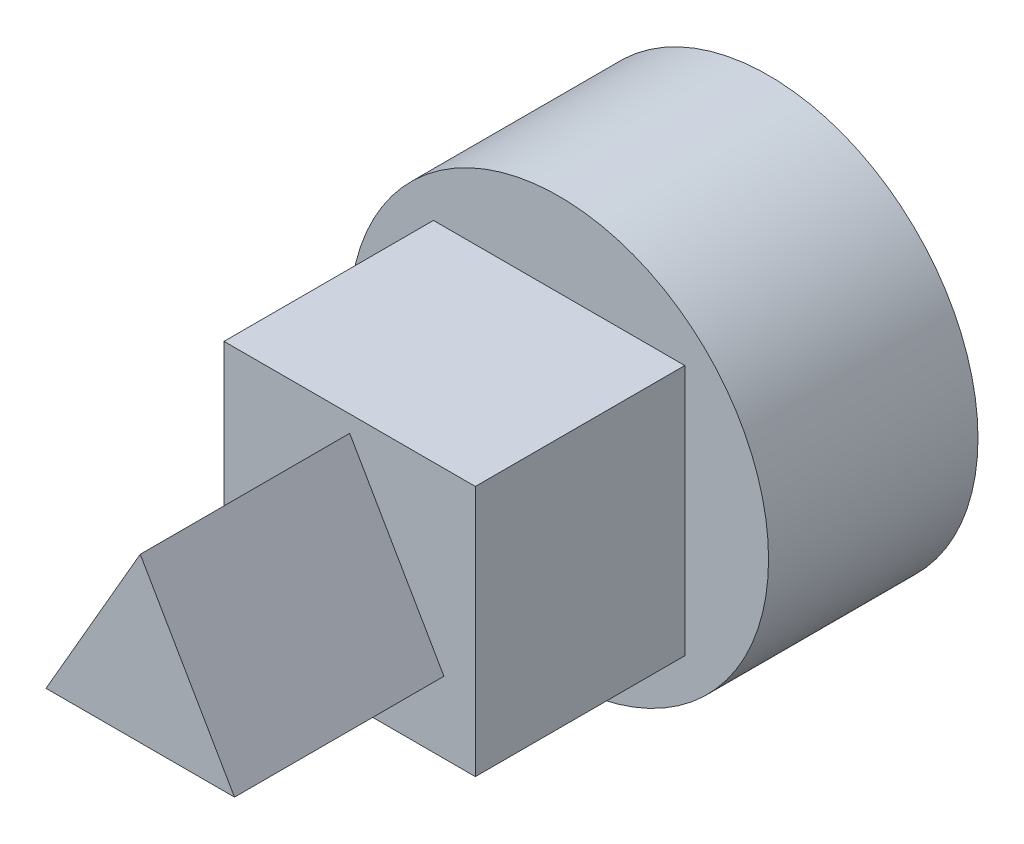
SolidWorks part; units mm, degrees
ref_plane "Front Plane" through (0, 0, 0) normal (0, 0, 1) x (1, 0, 0)
ref_plane "Top Plane" through (0, 0, 0) normal (0, 1, 0) x (1, 0, 0)
ref_plane "Right Plane" through (0, 0, 0) normal (1, 0, 0) x (0, 0, -1)
sketch "Sketch1" plane through (0, 0, 0) normal (0, 0, 1) x (1, 0, 0)
  line L1 (0, 25.9808) -> (-22.5, -12.9904)
  line L2 (-30, -30) -> (30, -30)
  line L3 (-30, -30) -> (-30, 30)
  line L4 (-30, 30) -> (30, 30)
  line L5 (30, -30) -> (30, 30)
  line L6 (-30, -30) -> (30, 30) construction
  line L7 (-30, 30) -> (30, -30) construction
  line L8 (-22.5, -12.9904) -> (22.5, -12.9904)
  line L9 (22.5, -12.9904) -> (0, 25.9808)
  circle A0 centre (0, 0) radius 50
  circle A1 centre (0, 0) radius 25.9808 construction
  point P4 (0, 0)
  dimension "D2" = 100
  dimension "D1" = 60
  dimension "D3" = 45
extrude "Boss-Extrude2" add sketch "Sketch1" along normal blind 150 contours L8 L9 L1 region at (0, 0, 0)
extrude "Boss-Extrude3" add sketch "Sketch1<4>" along normal blind 100 contours L2 L5 L4 L3 L9 L8 L1 region at (-29.1515, 0, 0)
sketch "Sketch1<4>" plane through (0, 0, 0) normal (0, 0, 1) x (1, 0, 0) same geometry as "Sketch1"
extrude "Boss-Extrude4" add sketch "Sketch1<5>" along normal blind 50 contours A0 L5 L2 L3 L4 region at (-48.5858, 0, 0)
sketch "Sketch1<5>" plane through (0, 0, 0) normal (0, 0, 1) x (1, 0, 0) same geometry as "Sketch1"
